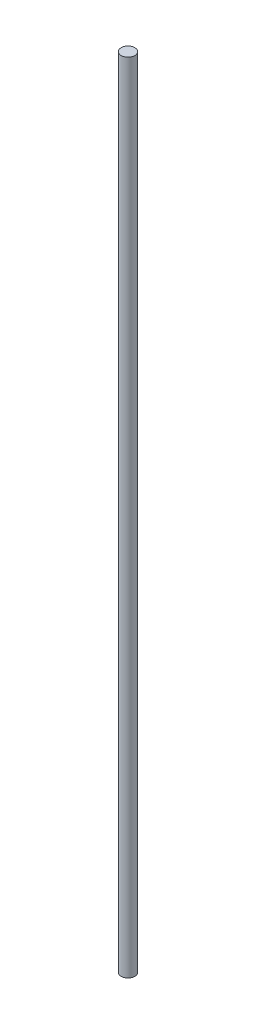
SolidWorks part; units mm, degrees
material "Pine"
ref_plane "Front" through (0, 0, 0) normal (0, 0, 1) x (1, 0, 0)
ref_plane "Top" through (0, 0, 0) normal (0, 1, 0) x (1, 0, 0)
ref_plane "Right" through (0, 0, 0) normal (1, 0, 0) x (0, 0, -1)
ref_axis "X" through (-80.9, 0, 0) along (1, 0, 0)
ref_axis "Y" through (0, -50, 0) along (0, 1, 0)
ref_axis "Z" through (0, 0, -80.9) along (0, 0, 1)
sketch "Sketch1" plane through (0, 0, 0) normal (0, 1, 0) x (1, 0, 0)
  circle A0 centre (0, 0) radius 1.5
  dimension "D1" = 3
extrude "Boss-Extrude1" add sketch "Sketch1" along normal mid plane 175
